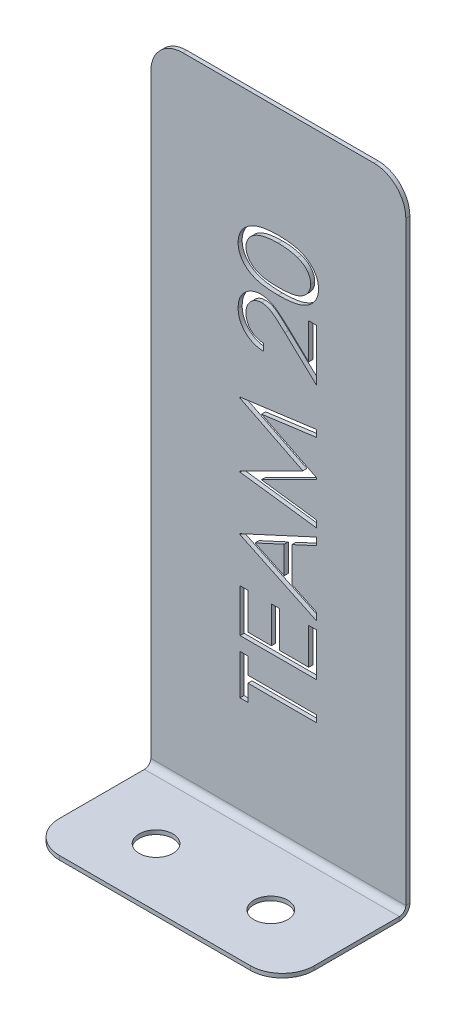
SolidWorks part; units mm, degrees
note: The reader was unsure of these and kept them because the rebuilt part matched: flange length of "Edge-Flange1".
ref_plane "Front Plane" through (0, 0, 0) normal (0, 0, 1) x (1, 0, 0)
ref_plane "Top Plane" through (0, 0, 0) normal (0, 1, 0) x (1, 0, 0)
ref_plane "Right Plane" through (0, 0, 0) normal (1, 0, 0) x (0, 0, -1)
sketch "Sketch1" plane through (0, 0, 0) normal (0, 0, 1) x (1, 0, 0)
  line L1 (-20, 50) -> (20, 50)
  line L2 (-20, 50) -> (-20, -50)
  line L3 (-20, -50) -> (20, -50)
  line L4 (20, 50) -> (20, -50)
  line L5 (-20, 50) -> (20, -50) construction
  line L6 (-20, -50) -> (20, 50) construction
  point P0 (0, 0)
  dimension "D1" = 100
  dimension "D2" = 40
base flange "Base-Flange1" sketch "Sketch1" thickness 0.635 reverse thickness direction no parameters "D1"=1
edge flange "Edge-Flange1" sketch "Sketch8" flange angle 90 flange length 20 flange position material inside bend radius 1 thickness 0.635 relief rectangular parameters "D6"=10
sketch "Sketch8" plane through (0, -50, 0) normal (0, -1, 0) x (1, 0, 0)
  line L0 (-20, 0) -> (20, 0) construction
  line L1 (-20, 0) -> (20, 0)
  line L2 (-20, 0) -> (-20, 19.365)
  line L3 (-20, 19.365) -> (20, 19.365)
  line L4 (20, 19.365) -> (20, 0)
bend "EdgeBend1" bend radius 1 bend angle 90 parameters "D5"=1
sketch "Sketch9" plane through (0, -49.365, 0) normal (0, 1, 0) x (1, 0, 0)
  line L0 (-20, -10.1825) -> (20, -10.1825) construction
  line L1 (-20, -19.365) -> (-20, -1) construction
  line L2 (20, -1) -> (20, -19.365) construction
  circle A0 centre (-9, -10.1825) radius 2.65
  circle A1 centre (9, -10.1825) radius 2.65
  dimension "D3" = 5.3
  dimension "D1" = 9
  dimension "D2" = 9
extrude "Cut-Extrude1" cut sketch "Sketch9" against normal through all normal cut yes
fillet "Fillet1" radius 5 4 edges at (-20, -49.6825, 19.365) (20, -49.6825, 19.365) (-20, 50, -0.3175) (20, 50, -0.3175)
sketch "Sketch10" plane through (0, 0, 0) normal (0, 0, 1) x (1, 0, 0)
  line L0 (6, 40) -> (6, -40) construction
  text T0 "TEAM 20\r\n" font "Century Gothic" height 12
  point P2 (6, 0)
  dimension "D1" = 80
  dimension "D2" = 6
extrude "Cut-Extrude2" cut sketch "Sketch10" against normal through all normal cut yes
sketch "Bend-Lines1" [suppressed] plane through (0, 0, 0) normal (0, 1, 0) x (1, 0, 0)
sketch "Bounding-Box1" [suppressed] plane through (0, 0, 0) normal (0, 1, 0) x (1, 0, 0)
other "Bend-Notch1" [suppressed] parameters "D1"=0, "D3"=5, "D2"=5
sheet metal parameters "Sheet-Metal1" thickness 0.635 parameters "D1"=1
flat pattern "Flat-Pattern1" [suppressed]
sketch "Bend-Lines2" plane through (0, 0, 0) normal (0, 1, 0) x (1, 0, 0)
sketch3d "Bounding-Box2" [suppressed]
  line L0 (-20, 100, 0) -> (-20, -100, 0) construction
  line L1 (20, 100, 0) -> (20, -100, 0) construction
  line L2 (-20, 100, 0) -> (20, 100, 0) construction
  line L3 (-20, -100, 0) -> (20, -100, 0) construction
sheet metal parameters "Sheet-Metal2" thickness 0.635 parameters "D1"=1
flat pattern "Flat-Pattern1"
sketch "Bend-Lines2" plane through (0, 0, 0) normal (0, 0, 1) x (1, 0, 0)
  line L0 (-20, -99.3998) -> (20, -99.3998) construction
  line L1 (-20, -99.3998) -> (20, -99.3998) construction
sketch3d "Bounding-Box2" [suppressed]
  line L0 (20, 100, 0) -> (20, -118.7995, 0) construction
  line L1 (-20, 100, 0) -> (-20, -118.7995, 0) construction
  line L2 (20, 100, 0) -> (-20, 100, 0) construction
  line L3 (20, -118.7995, 0) -> (-20, -118.7995, 0) construction
bend of the flat pattern "Flatten-<EdgeBend1>1"
sheet metal parameters "Sheet-Metal3" thickness 0.635 parameters "D1"=1
flat pattern "Flat-Pattern1"
sketch "Bend-Lines2" plane through (0, 0, 0) normal (0, 0, 1) x (1, 0, 0)
  line L0 (-20, -49.3998) -> (20, -49.3998) construction
  line L1 (-20, -49.3998) -> (20, -49.3998) construction
sketch3d "Bounding-Box2" [suppressed]
  line L0 (20, -68.7995, 0) -> (20, 50, 0) construction
  line L1 (-20, -68.7995, 0) -> (-20, 50, 0) construction
  line L2 (20, -68.7995, 0) -> (-20, -68.7995, 0) construction
  line L3 (20, 50, 0) -> (-20, 50, 0) construction
bend of the flat pattern "Flatten-<EdgeBend1>1"
sheet metal parameters "Sheet-Metal4" thickness 0.635 parameters "D1"=1
flat pattern "Flat-Pattern4"
sketch "Bend-Lines3" plane through (0, 0, 0) normal (0, 0, 1) x (1, 0, 0)
  line L0 (-20, -49.3998) -> (20, -49.3998) construction
  line L1 (-20, -49.3998) -> (20, -49.3998) construction
sketch3d "Bounding-Box3" [suppressed]
  line L0 (20, -68.7995, 0) -> (20, 50, 0) construction
  line L1 (-20, -68.7995, 0) -> (-20, 50, 0) construction
  line L2 (20, -68.7995, 0) -> (-20, -68.7995, 0) construction
  line L3 (20, 50, 0) -> (-20, 50, 0) construction
bend of the flat pattern "Flatten-<EdgeBend1>2"
sheet metal parameters "Sheet-Metal5" thickness 0.635 parameters "D1"=1
flat pattern "Flat-Pattern5"
sketch "Bend-Lines4" plane through (0, 0, 0) normal (0, 1, 0) x (1, 0, 0)
sketch3d "Bounding-Box4" [suppressed]
  line L0 (-5.0685, 25.601, 0) -> (5.0853, 25.6298, 0) construction
  line L1 (-5.0855, 31.601, 0) -> (5.0683, 31.6297, 0) construction
  line L2 (-5.0685, 25.601, 0) -> (-5.0855, 31.601, 0) construction
  line L3 (5.0853, 25.6298, 0) -> (5.0683, 31.6297, 0) construction
sheet metal parameters "Sheet-Metal6" thickness 0.635 parameters "D1"=1
flat pattern "Flat-Pattern6"
sketch "Bend-Lines5" plane through (0, 0, 0) normal (0, 1, 0) x (1, 0, 0)
sketch3d "Bounding-Box5" [suppressed]
  line L0 (-3.6587, -13.1058, 0) -> (0.9231, -13.1058, 0) construction
  line L1 (-3.6587, -8.8197, 0) -> (0.9231, -8.8197, 0) construction
  line L2 (-3.6587, -13.1058, 0) -> (-3.6587, -8.8197, 0) construction
  line L3 (0.9231, -13.1058, 0) -> (0.9231, -8.8197, 0) construction
